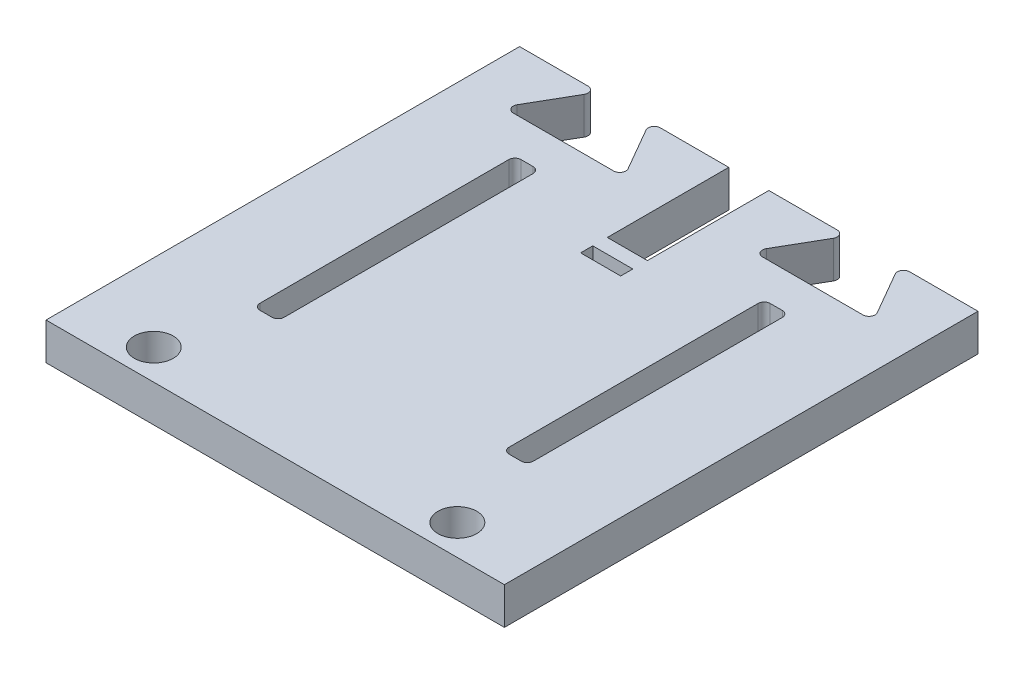
SolidWorks part; units mm, degrees
ref_plane "Front Plane" through (0, 0, 0) normal (0, 0, 1) x (1, 0, 0)
ref_plane "Top Plane" through (0, 0, 0) normal (0, 1, 0) x (1, 0, 0)
ref_plane "Right Plane" through (0, 0, 0) normal (1, 0, 0) x (0, 0, -1)
sketch "Sketch1" plane through (0, 0, 0) normal (0, 1, 0) x (1, 0, 0)
  line L0 (-19.375, 0) -> (-19.375, 39)
  line L1 (-19.375, 39) -> (-12.375, 39)
  line L2 (-12.375, 39) -> (-15.2618, 34)
  line L3 (-15.2618, 34) -> (-5.2618, 34)
  line L4 (-5.2618, 34) -> (-8.1485, 39)
  line L5 (-8.1485, 39) -> (8.1485, 39)
  line L6 (8.1485, 39) -> (5.2618, 34)
  line L7 (5.2618, 34) -> (15.2618, 34)
  line L8 (15.2618, 34) -> (12.375, 39)
  line L9 (12.375, 39) -> (19.375, 39)
  line L10 (19.375, 39) -> (19.375, 0)
  line L11 (19.375, 0) -> (-19.375, 0)
  point P3 (0, 0)
  dimension "D1" = 39
  dimension "D2" = 38.75
  dimension "D3" = 7
  dimension "D4" = 10
  dimension "D5" = 10
  dimension "D6" = 7
  dimension "D7" = 5
  dimension "D11" = 60
  dimension "D12" = 60
  dimension "D13" = 60
extrude "Boss-Extrude1" add sketch "Sketch1" along normal blind 3.05
fillet "Fillet3" radius 0.5 8 edges at (15.2618, 1.525, -34) (12.375, 1.525, -39) (5.2618, 1.525, -34) (8.1485, 1.525, -39) (-8.1485, 1.525, -39) (-5.2618, 1.525, -34) (-15.2618, 1.525, -34) (-12.375, 1.525, -39)
sketch "Sketch2" plane through (0, 3.05, 0) normal (0, 1, 0) x (1, 0, 0)
  line L0 (0, 0) -> (0, 32.5) construction
  line L3 (1.65, 29) -> (-1.65, 29)
  line L4 (1.65, 29) -> (1.65, 76)
  line L5 (1.65, 76) -> (-1.65, 76)
  line L6 (-1.65, 29) -> (-1.65, 76)
  line L7 (-1.65, 27.8) -> (1.65, 27.8)
  line L8 (-1.65, 27.8) -> (-1.65, 26.8)
  line L9 (-1.65, 26.8) -> (1.65, 26.8)
  line L10 (1.65, 27.8) -> (1.65, 26.8)
  line L11 (-19.375, 0) -> (19.375, 0) construction
  line L12 (-19.375, 0) -> (-19.375, 82.5) construction
  line L13 (-19.375, 82.5) -> (19.375, 82.5) construction
  line L14 (19.375, 0) -> (19.375, 82.5) construction
  point P8 (0, 29)
  point P13 (0, 27.8)
  dimension "D1" = 3.3
  dimension "D2" = 47
  dimension "D3" = 1
  dimension "D4" = 1.2
  dimension "D5" = 82.5
  dimension "D6" = 6.5
extrude "Cut-Extrude1" cut sketch "Sketch2" against normal through all
sketch "Sketch6" plane through (0, 3.05, 0) normal (0, 1, 0) x (1, 0, 0)
  line L0 (0, 0) -> (0, 18.0616) construction
  line L1 (-6.1278, 34) -> (-14.3957, 34) construction
  line L2 (-11.2618, 31) -> (-9.2618, 31)
  line L3 (-11.2618, 31) -> (-11.2618, 9.5)
  line L4 (-11.2618, 9.5) -> (-9.2618, 9.5)
  line L5 (-9.2618, 31) -> (-9.2618, 9.5)
  line L7 (11.2618, 9.5) -> (9.2618, 9.5)
  line L8 (9.2618, 31) -> (9.2618, 9.5)
  line L9 (11.2618, 31) -> (9.2618, 31)
  line L10 (11.2618, 31) -> (11.2618, 9.5)
  line L11 (-19.375, 0) -> (19.375, 0) construction
  point P9 (-10.2618, 34)
  point P10 (-10.2618, 31)
  dimension "D1" = 2
  dimension "D2" = 3
  dimension "D3" = 9.5
extrude "Cut-Extrude2" cut sketch "Sketch6" against normal through all
fillet "Fillet4" radius 0.5 8 edges at (9.2618, 1.525, -9.5) (11.2618, 1.525, -9.5) (11.2618, 1.525, -31) (9.2618, 1.525, -31) (-11.2618, 1.525, -9.5) (-9.2618, 1.525, -9.5) (-9.2618, 1.525, -31) (-11.2618, 1.525, -31)
sketch "Head Mounting Hole Locations" plane through (0, 3.05, 0) normal (0, 1, 0) x (1, 0, 0)
  line L0 (0, 0) -> (0, 16.3288) construction
  line L1 (-19.375, 0) -> (19.375, 0) construction
  circle A0 centre (-12.5, 2.5) radius 1.5
  circle A1 centre (12.5, 2.5) radius 1.5
  dimension "D1" = 3
  dimension "D2" = 12.5
  dimension "D3" = 2.5
hole_wizard "M3 Clearance Head Mounting Holes" positions "Sketch4" profile "Sketch5" hole size "M3" standard "ANSI Metric" end condition through all
sketch "Sketch4" plane through (0, 3.05, 0) normal (0, 1, 0) x (1, 0, 0)
  point P0 (-12.5, 2.5)
  point P3 (12.5, 2.5)
sketch "Sketch5" plane through (-12.5, 3.05, -2.5) normal (1, 0, 0) x (0, 0, 1)
  line L0 (0, 0) -> (0, 3.05)
  line L1 (0, 3.05) -> (1.6, 3.05)
  line L2 (1.6, 3.05) -> (1.6, 0)
  line L5 (1.6, 0) -> (0, 0)
  line L11 (0, -6.35) -> (0, 107.95) construction
  dimension "Thru Hole Dia." = 3.2
  dimension "Thru Hole Depth" = 3.05
sketch "Sketch7" plane through (0, 3.05, 0) normal (0, 1, 0) x (1, 0, 0)
  line L0 (-19.375, 39) -> (-18.875, 39)
  line L1 (-13.241, 39) -> (-19.375, 39) construction
  line L2 (-18.875, 39) -> (-18.875, 0)
  line L3 (-19.375, 0) -> (19.375, 0) construction
  line L4 (-18.875, 0) -> (-19.375, 0)
  line L5 (-19.375, 0) -> (-19.375, 39)
  line L6 (19.375, 39) -> (18.875, 39)
  line L7 (19.375, 39) -> (13.241, 39) construction
  line L8 (18.875, 39) -> (18.875, 0)
  line L9 (18.875, 0) -> (19.375, 0)
  line L10 (19.375, 0) -> (19.375, 39)
  dimension "D1" = 0.5
  dimension "D2" = 0.5
extrude "Cut-Extrude3" cut sketch "Sketch7" against normal through all
